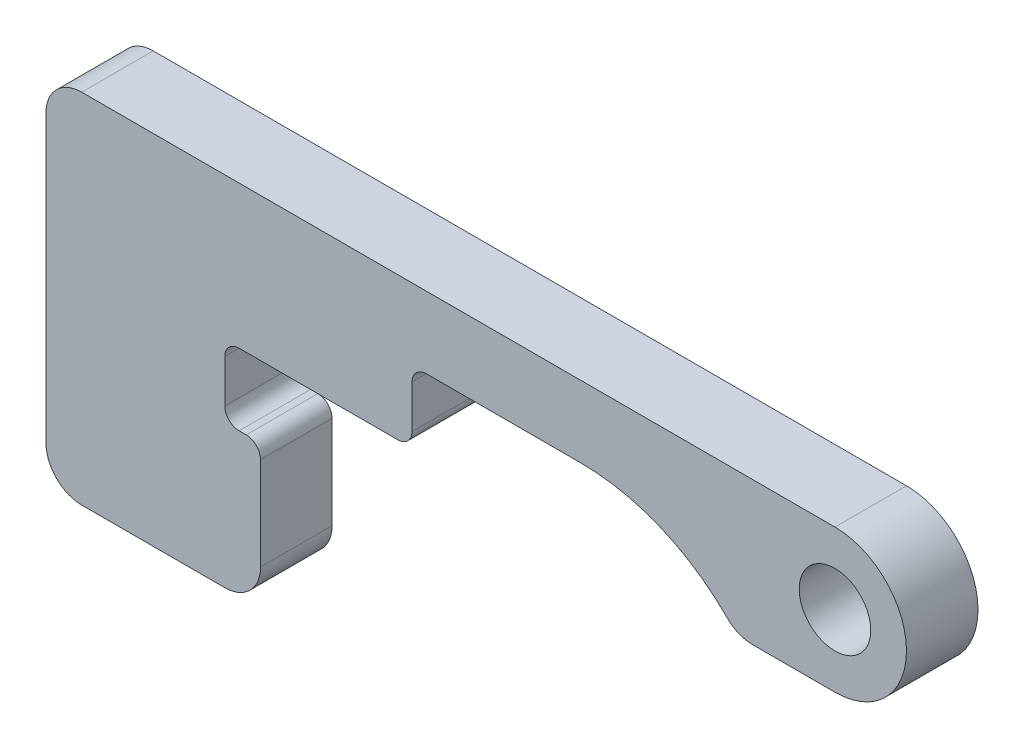
SolidWorks part; units mm, degrees
ref_plane "Front Plane" through (0, 0, 0) normal (0, 0, 1) x (1, 0, 0)
ref_plane "Top Plane" through (0, 0, 0) normal (0, 1, 0) x (1, 0, 0)
ref_plane "Right Plane" through (0, 0, 0) normal (1, 0, 0) x (0, 0, -1)
sketch "Sketch1" plane through (0, 0, 0) normal (0, 0, 1) x (1, 0, 0)
  line L0 (-80.3169, -40) -> (-110.3169, -40)
  line L1 (-110.3169, -40) -> (-110.3169, 10)
  line L2 (-110.3169, 10) -> (0, 10)
  line L4 (0, -10) -> (-13.704, -10)
  line L5 (-59.1384, -10) -> (-85.3169, -10)
  line L6 (-85.3169, -10) -> (-85.3169, -20)
  line L7 (-85.3169, -20) -> (-80.3169, -20)
  line L8 (-80.3169, -20) -> (-80.3169, -40)
  line L9 (-59.1384, -10) -> (-59.1384, 0)
  line L10 (-59.1384, 0) -> (-35.5537, 0)
  arc A1 (-13.704, -10) -> (-35.5537, 0) centre (-35.5537, -28.8705) ccw
  circle A3 centre (0, 0) radius 5
  arc A4 (0, -10) -> (0, 10) centre (0, 0) ccw
  point P2 (157.9367, 55.4854)
  point P3 (247.9217, 72.8736)
  point P7 (121.3289, 71.4457)
  point P10 (165.4152, 67.0072)
  point P11 (190.7956, 76.1877)
  point P18 (94.706, 44.2821)
  point P19 (124.2272, 30.5723)
  point P20 (149.276, 39.6564)
  point P21 (138.3375, 30)
  point P22 (108.8463, 40)
  point P25 (0, 0)
  point P26 (0, 0)
  point P27 (107.8436, 53.6271)
  point P28 (0, 0)
  point P30 (-77.9568, 0)
  point P31 (-32.4585, -10)
  point P32 (-51.4387, -10)
  point P33 (-72.2388, 0)
  point P34 (-35.5537, 0)
  dimension "D5" = 10
  dimension "D6" = 20
  dimension "D1" = 25
  dimension "D2" = 5
  dimension "D3" = 20
  dimension "D4" = 20
  dimension "D7" = 10
  dimension "D8" = 10
extrude "Boss-Extrude1" add sketch "Sketch1" along normal blind 10
fillet "Fillet1" radius 5 4 edges at (-13.704, -10, 5) (-110.3169, 10, 5) (-80.3169, -40, 5) (-110.3169, -40, 5)
fillet "Fillet2" radius 2 5 edges at (-59.1384, 0, 5) (-59.1384, -10, 5) (-85.3169, -10, 5) (-85.3169, -20, 5) (-80.3169, -20, 5)
